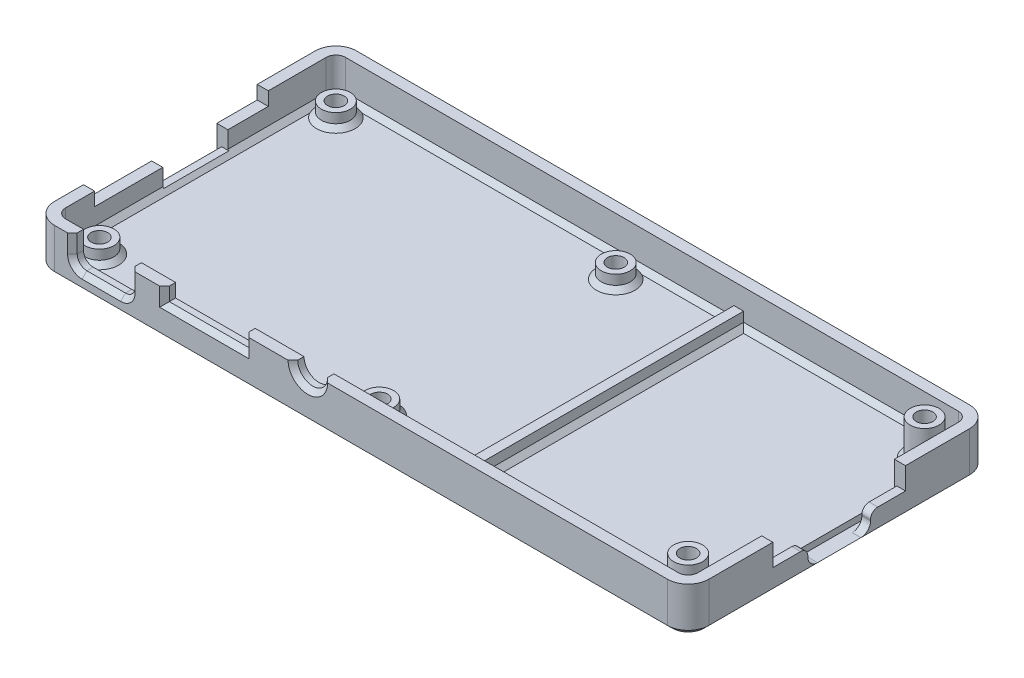
SolidWorks part; units mm, degrees
ref_plane "Front Plane" through (0, 0, 0) normal (0, 0, 1) x (1, 0, 0)
ref_plane "Top Plane" through (0, 0, 0) normal (0, 1, 0) x (1, 0, 0)
ref_plane "Right Plane" through (0, 0, 0) normal (1, 0, 0) x (0, 0, -1)
sketch "Sketch1" plane through (0, 0, 0) normal (0, 1, 0) x (1, 0, 0)
  line L0 (-71.5618, 3.106) -> (57.4382, 3.106) construction
  line L1 (-71.5618, 31.106) -> (57.4382, 31.106)
  line L2 (-71.5618, 31.106) -> (-71.5618, -24.894)
  line L3 (-71.5618, -24.894) -> (57.4382, -24.894)
  line L4 (57.4382, 31.106) -> (57.4382, -24.894)
  line L5 (-60.6618, -24.894) -> (-60.6618, -31.6828) construction
  line L6 (-68.0618, 27.606) -> (-10.0618, 27.606)
  line L7 (-68.0618, 27.606) -> (-68.0618, -21.394)
  line L8 (-68.0618, -21.394) -> (-10.0618, -21.394)
  line L9 (-10.0618, 27.606) -> (-10.0618, -21.394)
  line L10 (-39.5618, -24.894) -> (-39.5618, -31.6828) construction
  line L11 (-18.0618, -24.894) -> (-18.0618, -31.6828) construction
  line L12 (-65.4118, -26.5648) -> (-55.9118, -26.5648) construction
  line L13 (-48.0618, -26.5648) -> (-31.0618, -26.5648) construction
  line L14 (-22.0618, -26.5648) -> (-14.0618, -26.5648) construction
  line L15 (-72.5618, 9.606) -> (-72.5618, -3.394) construction
  line L16 (-71.5618, 3.106) -> (-72.5618, 3.106) construction
  dimension "D1" = 129
  dimension "D2" = 56
  dimension "D3" = 49
  dimension "D4" = 58
  dimension "D5" = 3.5
  dimension "D6" = 3.5
  dimension "D7" = 10.9
  dimension "D8" = 32
  dimension "D9" = 53.5
  dimension "D10" = 2
  dimension "D11" = 13
  dimension "D12" = 9.5
  dimension "D13" = 17
  dimension "D14" = 8
sketch "Sketch3" plane through (0, 0, 0) normal (0, 1, 0) x (1, 0, 0)
  line L4 (60.7382, 34.406) -> (-74.8618, 34.406)
  line L5 (-74.8618, 34.406) -> (-74.8618, -28.194)
  line L6 (-74.8618, -28.194) -> (60.7382, -28.194)
  line L7 (60.7382, -28.194) -> (60.7382, 34.406)
  line L8 (58.4382, 32.106) -> (-72.5618, 32.106)
  line L9 (58.4382, -25.894) -> (58.4382, 32.106)
  line L10 (-72.5618, -25.894) -> (58.4382, -25.894)
  line L11 (-72.5618, 32.106) -> (-72.5618, -25.894)
  line L12 (58.4382, 32.106) -> (-72.5618, 32.106)
  line L13 (58.4382, -25.894) -> (58.4382, 32.106)
  line L14 (-72.5618, -25.894) -> (58.4382, -25.894)
  line L15 (-72.5618, 32.106) -> (-72.5618, -25.894)
  line L16 (-7.0618, 3.106) -> (-7.0618, 34.406) construction
  line L17 (-71.5618, 3.106) -> (57.4382, 3.106) construction
  line L20 (-74.8618, 3.106) -> (52.7382, 3.106) construction
  line L25 (60.7382, -28.194) -> (60.7382, 34.406) construction
  line L26 (58.4382, -25.894) -> (58.4382, 32.106) construction
  dimension "D1" = 1
  dimension "D2" = 2.3
extrude "Boss-Extrude1" add sketch "Sketch3" along normal blind 9.3
sketch "Sketch5" plane through (0, 0, 0) normal (0, 1, 0) x (1, 0, 0)
  line L1 (-72.5618, 32.106) -> (58.4382, 32.106)
  line L2 (-72.5618, 32.106) -> (-72.5618, -25.894)
  line L3 (-72.5618, -25.894) -> (58.4382, -25.894)
  line L4 (58.4382, 32.106) -> (58.4382, -25.894)
extrude "Boss-Extrude2" add sketch "Sketch5" along normal blind 2
sketch "Sketch6" plane through (0, 2, 0) normal (0, 1, 0) x (1, 0, 0)
  circle A0 centre (-68.0618, 27.606) radius 3
  circle A1 centre (-68.0618, -21.394) radius 3
  circle A2 centre (-10.0618, -21.394) radius 3
  circle A3 centre (-10.0618, 27.606) radius 3
extrude "Boss-Extrude3" add sketch "Sketch6" along normal offset from surface (3 mm away) 4.3 up to face at (-7.0618, 9.3, -3.106)
sketch "Sketch10" plane through (0, 2, 0) normal (0, 1, 0) x (1, 0, 0)
  line L0 (58.4382, 32.106) -> (-72.5618, 32.106) construction
  line L1 (9.9382, 32.106) -> (11.9382, 32.106)
  line L2 (9.9382, 32.106) -> (9.9382, -25.894)
  line L3 (9.9382, -25.894) -> (11.9382, -25.894)
  line L4 (11.9382, 32.106) -> (11.9382, -25.894)
  line L5 (-72.5618, -25.894) -> (58.4382, -25.894) construction
  line L6 (-10.0618, 27.606) -> (-10.0618, -21.394) construction
  dimension "D1" = 2
  dimension "D2" = 20
extrude "Boss-Extrude4" add sketch "Sketch10" along normal offset from surface (3 mm away) 4.3 up to face at (-7.0618, 9.3, -3.106)
sketch "Sketch11" plane through (0, 0, 28.194) normal (0, 0, 1) x (1, 0, 0)
  line L0 (-74.8618, 9.3) -> (-74.8618, 0) construction
  line L1 (-66.8618, 9.3) -> (-54.8618, 9.3)
  line L2 (-66.8618, 9.3) -> (-66.8618, 3.5)
  line L3 (-66.8618, 3.5) -> (-54.8618, 3.5)
  line L4 (-54.8618, 9.3) -> (-54.8618, 3.5)
  line L6 (-60.8618, 9.3) -> (-60.6618, 0) construction
  line L7 (-65.4118, 0) -> (-55.9118, 0) construction
  line L9 (-47.778, 9.3) -> (-31.278, 9.3)
  line L10 (-47.778, 9.3) -> (-47.778, 6.5)
  line L11 (-47.778, 6.5) -> (-31.278, 6.5)
  line L12 (-31.278, 9.3) -> (-31.278, 6.5)
  line L14 (-39.5618, 0) -> (-39.528, 9.3) construction
  line L15 (-48.0618, 0) -> (-31.0618, 0) construction
  line L16 (-18.0618, 0) -> (-18.0618, 9.3) construction
  line L17 (-22.0618, 0) -> (-14.0618, 0) construction
  line L18 (-74.8618, 9.3) -> (60.7382, 9.3) construction
  circle A0 centre (-18.0618, 9.3) radius 3.1
  dimension "D5" = 6.2
  dimension "D1" = 0
  dimension "D2" = 12
  dimension "D3" = 0
  dimension "D4" = 16.5
  dimension "D6" = 8
  dimension "D7" = 5.8
  dimension "D8" = 2.8
extrude "Cut-Extrude1" cut sketch "Sketch11" against normal up to next
sketch "Sketch12" plane through (-74.8618, 0, 0) normal (-1, 0, 0) x (0, 0, 1)
  line L0 (-3.106, 0) -> (-3.106, 9.3) construction
  line L1 (-27.606, 0) -> (21.394, 0) construction
  line L2 (-34.406, 9.3) -> (28.194, 9.3) construction
  line L3 (-24.106, 6.5) -> (17.894, 6.5)
  line L4 (-9.7329, 6.5) -> (3.7671, 6.5)
  line L5 (-9.7329, 6.5) -> (-9.7329, 2.8)
  line L6 (-9.7329, 2.8) -> (3.7671, 2.8)
  line L7 (3.7671, 6.5) -> (3.7671, 2.8)
  line L8 (-24.106, 9.3) -> (17.894, 9.3)
  line L9 (-24.106, 9.3) -> (-24.106, 6.5)
  line L10 (-24.106, 6.5) -> (-24.106, 9.3)
  line L11 (17.894, 9.3) -> (17.894, 6.5)
  line L12 (-9.7329, 4.65) -> (3.7671, 4.65) construction
  line L13 (-24.106, 9.3) -> (-24.106, 6.5)
  point P17 (-3.106, 6.5)
  dimension "D1" = 13.5
  dimension "D2" = 2.8
  dimension "D3" = 3.7
  dimension "D4" = 6.5
extrude "Cut-Extrude2" cut sketch "Sketch12" against normal up to next contours L3 L11 L8 L13 L9 L10 | L7 L6 L5 L4
fillet "Fillet6" radius 2 1 edges at (58.4382, 5.65, -32.106)
fillet "Fillet8" radius 2 2 edges at (-72.5618, 5.65, 25.894) (-72.5618, 5.65, -32.106)
chamfer "Chamfer1" distance 1 angle 45 4 edges at (-68.0618, 2, 24.394) (-10.0618, 2, 24.394) (-10.0618, 2, -24.606) (-68.0618, 2, -24.606)
sketch "Sketch24" plane through (0, 2, 0) normal (0, 1, 0) x (1, 0, 0)
  line L0 (11.9382, 3.106) -> (61.5789, 3.106) construction
  line L1 (11.9382, -25.894) -> (11.9382, 32.106) construction
  line L2 (53.9382, -18.394) -> (58.4382, -18.394)
  line L3 (58.4382, -25.894) -> (58.4382, 30.106) construction
  line L4 (-68.0618, 27.606) -> (-10.0618, 27.606) construction
  line L5 (-68.0618, 27.606) -> (-68.0618, -21.394) construction
  line L6 (-68.0618, -21.394) -> (-10.0618, -21.394) construction
  line L7 (-10.0618, 27.606) -> (-10.0618, -21.394) construction
  line L8 (-10.0618, 27.606) -> (53.9382, 27.606) construction
  line L9 (-10.0618, 27.606) -> (-10.0618, -21.394) construction
  line L10 (-10.0618, -21.394) -> (53.9382, -21.394) construction
  line L11 (53.9382, 27.606) -> (53.9382, -21.394) construction
  line L12 (50.9382, -21.394) -> (50.9382, -25.894)
  line L13 (11.9382, -25.894) -> (58.4382, -25.894) construction
  line L14 (58.4382, -25.894) -> (58.4382, 30.106) construction
  line L15 (58.4382, -18.394) -> (58.4382, -25.894)
  line L16 (58.4382, -25.894) -> (50.9382, -25.894)
  line L17 (50.9382, 27.606) -> (50.9382, 32.106)
  line L18 (56.4382, 32.106) -> (-70.5618, 32.106) construction
  line L19 (53.9382, 24.606) -> (58.4382, 24.606)
  line L20 (58.4382, 24.606) -> (58.4382, 32.106)
  line L21 (58.4382, 32.106) -> (50.9382, 32.106)
  arc A0 (50.9382, -21.394) -> (53.9382, -18.394) centre (53.9382, -21.394) cw
  arc A1 (50.9382, 27.606) -> (53.9382, 24.606) centre (53.9382, 27.606) ccw
  dimension "D2" = 4.5
extrude "Boss-Extrude7" add sketch "Sketch24" along normal up to surface (7.3 mm away) up to face at (-8.3784, 9.3, -11.175)
fillet "Fillet20" radius 4.3 4 edges at (60.7382, 4.65, 28.194) (-74.8618, 4.65, -34.406) (-74.8618, 4.65, 28.194) (60.7382, 4.65, -34.406)
chamfer "Chamfer5" distance 1 angle 45 10 edges at (-71.976, 2, 25.3082) (-71.976, 2, -31.5202) (-30.3118, 2, 25.894) (-30.3118, 2, -32.106) (9.9382, 2, -3.106) (11.9382, 2, -3.106) (31.4382, 2, -32.106) (31.4382, 2, 25.894) (58.4382, 2, -3.106) (-72.5618, 2, -3.106)
hole_wizard "CSK for #4 Flat Head Socket Cap Screw1" positions "Sketch28" profile "Sketch27" countersink size "#4" standard "ANSI Inch"
sketch "Sketch28" plane through (0, 0, 0) normal (0, -1, 0) x (-1, 0, 0)
  point P0 (68.0618, 27.606)
  point P4 (68.0618, -21.394)
  point P8 (-53.9382, 27.606)
  point P12 (-53.9382, -21.394)
  point P15 (10.0618, -21.394)
  point P19 (10.0618, 27.606)
sketch "Sketch27" plane through (-68.0618, 0, -27.606) normal (1, 0, 0) x (0, 0, -1)
  line L0 (0, 0) -> (0, 15.0378)
  line L1 (0, 15.0378) -> (1.7272, 14)
  line L2 (1.7272, 14) -> (1.7272, 1.8805)
  line L3 (1.7272, 1.8805) -> (3.3619, 0)
  line L5 (3.3619, 0) -> (0, 0)
  line L6 (-1.7272, 1.8805) -> (-3.3619, 0) construction
  line L10 (0, 15.0378) -> (-1.7272, 14) construction
  line L11 (0, -6.35) -> (0, 107.95) construction
  dimension "Hole Dia." = 3.4544
  dimension "Hole Depth" = 14
  dimension "Near C'Sink Dia." = 6.7238
  dimension "Near C'Sink Angle" = 82
  dimension "Drill Angle" = 118
chamfer "Chamfer7" distance 1 angle 45 8 edges at (-74.8618, 0, -3.106) (-73.6023, 0, 26.9346) (-73.6023, 0, -33.1466) (-7.0618, 0, 28.194) (-7.0618, 0, -34.406) (59.4788, 0, 26.9346) (59.4788, 0, -33.1466) (60.7382, 0, -3.106)
chamfer "Chamfer8" distance 1 angle 45 1 edges at (-74.8618, 2.8, -2.9829)
sketch "Sketch29" plane through (0, 9.3, 0) normal (0, 1, 0) x (1, 0, 0)
  line L0 (53.9382, 24.606) -> (58.4382, 24.606)
  line L1 (58.4382, 24.606) -> (58.4382, 30.106)
  line L2 (56.4382, 32.106) -> (50.9382, 32.106)
  line L3 (50.9382, 32.106) -> (50.9382, 27.606)
  line L4 (53.9382, -18.394) -> (58.4382, -18.394)
  line L5 (58.4382, -18.394) -> (58.4382, -23.894)
  line L6 (56.4382, -25.894) -> (50.9382, -25.894)
  line L7 (50.9382, -25.894) -> (50.9382, -21.394)
  arc A0 (53.9382, 24.606) -> (50.9382, 27.606) centre (53.9382, 27.606) ccw
  arc A1 (56.4382, 32.106) -> (58.4382, 30.106) centre (56.4382, 30.106) cw
  arc A2 (50.9382, -21.394) -> (53.9382, -18.394) centre (53.9382, -21.394) ccw
  arc A3 (56.4382, -25.894) -> (58.4382, -23.894) centre (56.4382, -23.894) ccw
extrude "Cut-Extrude3" cut sketch "Sketch29" against normal up to surface (7.3 mm away) up to face at (45.114, 2, -3.106)
fillet "Fillet21" radius 2 2 edges at (-54.8618, 3.5, 27.044) (-66.8618, 3.5, 27.044)
chamfer "Chamfer9" distance 1 angle 45 9 edges at (-18.0618, 6.2, 28.194) (-31.278, 7.9, 28.194) (-39.528, 6.5, 28.194) (-47.778, 7.9, 28.194) (-54.8618, 7.4, 28.194) (-55.4476, 4.0858, 28.194) (-60.8618, 3.5, 28.194) (-66.276, 4.0858, 28.194) (-66.8618, 7.4, 28.194)
sketch "Sketch30" plane through (58.4382, 0, 0) normal (-1, 0, 0) x (0, 0, 1)
  line L1 (-16.856, 28.5) -> (10.644, 28.5)
  line L2 (-16.856, 28.5) -> (-16.856, 1)
  line L3 (-16.856, 1) -> (10.644, 1)
  line L4 (10.644, 28.5) -> (10.644, 1)
  dimension "D1" = 27.5
  dimension "D2" = 27.5
extrude "Cut-Extrude4" cut sketch "Sketch30" against normal blind 0.5 and the other way blind 0.7
sketch "Sketch31" plane through (58.9382, 0, 0) normal (-1, 0, 0) x (0, 0, 1)
  line L0 (-16.856, 3) -> (-16.856, 9.3) construction
  line L1 (-16.856, 4.75) -> (-11.106, 4.75)
  line L2 (-16.856, 4.75) -> (-16.856, 9.3)
  line L3 (-16.856, 9.3) -> (10.644, 9.3)
  line L4 (10.644, 4.75) -> (10.644, 9.3)
  line L5 (-30.106, 1) -> (23.894, 1) construction
  line L6 (4.894, 4.75) -> (10.644, 4.75)
  line L8 (-9.606, 3.25) -> (-9.606, 3)
  line L9 (-7.606, 1) -> (1.394, 1)
  line L10 (3.394, 3.25) -> (3.394, 3)
  arc A0 (3.394, 3.25) -> (4.894, 4.75) centre (4.894, 3.25) cw
  arc A1 (-11.106, 4.75) -> (-9.606, 3.25) centre (-11.106, 3.25) cw
  arc A2 (1.394, 1) -> (3.394, 3) centre (1.394, 3) ccw
  arc A3 (-9.606, 3) -> (-7.606, 1) centre (-7.606, 3) ccw
  dimension "D3" = 1.5
  dimension "D4" = 2
  dimension "D1" = 3.75
  dimension "D2" = 13
  dimension "D5" = 7.25
extrude "Cut-Extrude5" cut sketch "Sketch31" against normal through all
sketch "Sketch32" plane through (0, 6.5, 0) normal (0, 1, 0) x (1, 0, 0)
  line L0 (-74.8618, 24.106) -> (-74.8618, 9.7329) construction
  line L1 (-72.5618, 24.106) -> (-74.8618, 24.106)
  line L2 (-72.5618, 24.106) -> (-72.5618, 18.106)
  line L3 (-72.5618, 18.106) -> (-74.8618, 18.106)
  line L4 (-74.8618, 24.106) -> (-74.8618, 18.106)
  dimension "D1" = 6
extrude "Boss-Extrude8" add sketch "Sketch32" along normal up to vertex up to point (-72.5618, 9.3, -24.106)
chamfer "Chamfer10" distance 1 angle 45 5 edges at (57.8524, 2, 25.3082) (53.6882, 2, 25.894) (58.4382, 2, 21.144) (57.8524, 2, -31.5202) (53.6882, 2, -32.106)
chamfer "Chamfer11" distance 1 angle 45 2 edges at (53.9382, 2, 18.394) (53.9382, 2, -24.606)
